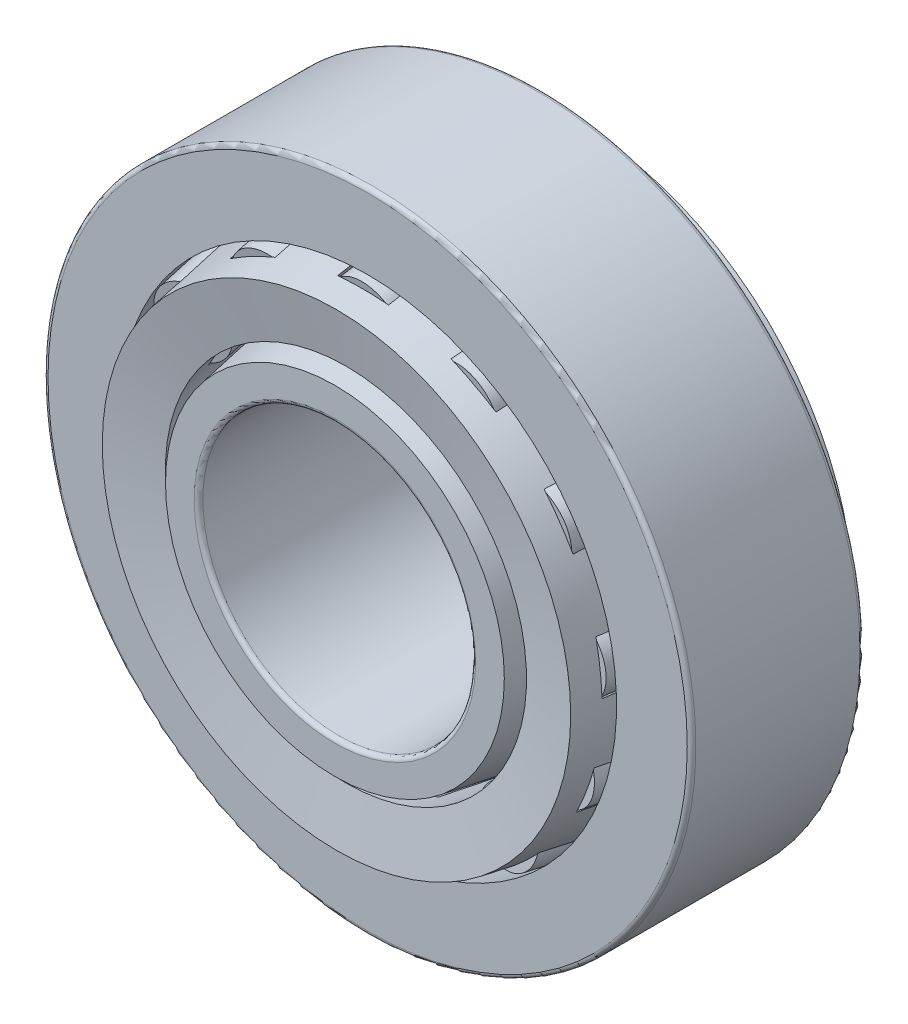
SolidWorks part; units mm, degrees
ref_plane "Front Plane" through (0, 0, 0) normal (0, 0, 1) x (1, 0, 0)
ref_plane "Top Plane" through (0, 0, 0) normal (0, 1, 0) x (1, 0, 0)
ref_plane "Right Plane" through (0, 0, 0) normal (1, 0, 0) x (0, 0, -1)
sketch "Sketch1" plane through (0, 0, 0) normal (1, 0, 0) x (0, 0, -1)
  line L0 (-8.3185, 0) -> (8.3185, 0) construction
  line L1 (0, 0) -> (0, 22.6219) construction
  line L2 (-8.3185, 9.525) -> (8.3185, 9.525) construction
  line L3 (8.3185, 9.525) -> (8.3185, 14.7638) construction
  line L4 (8.3185, 14.7638) -> (-8.3185, 11.8302) construction
  line L5 (-8.3185, 11.8302) -> (-8.3185, 9.525) construction
  line L7 (-6.0325, 22.6219) -> (6.0325, 22.6219)
  line L8 (6.0325, 22.6219) -> (6.0325, 19.5105)
  line L9 (6.0325, 19.5105) -> (-6.0325, 17.3831)
  line L10 (-6.0325, 17.3831) -> (-6.0325, 22.6219)
  line L12 (8.4538, 19.9375) -> (9.3345, 14.9429) construction
  line L13 (-7.4378, 11.9855) -> (-8.3185, 16.98) construction
  line L14 (-8.3185, 11.8302) -> (-7.4378, 11.9855) construction
  line L15 (-8.3185, 11.8302) -> (9.3345, 14.9429) construction
  line L20 (-8.3185, -11.8302) -> (9.3345, -14.9429) construction
  line L21 (-8.3185, -11.8302) -> (-7.4378, -11.9855) construction
  line L22 (-7.4378, -11.9855) -> (-8.3185, -16.98) construction
  line L23 (8.4538, -19.9375) -> (9.3345, -14.9429) construction
  line L24 (-8.3185, -11.8302) -> (-8.3185, -9.525) construction
  line L25 (8.3185, -14.7638) -> (-8.3185, -11.8302) construction
  line L26 (8.3185, -9.525) -> (8.3185, -14.7638) construction
  line L27 (-8.3185, -9.525) -> (8.3185, -9.525) construction
  line L28 (-6.0325, -17.3831) -> (-6.0325, -22.6219) construction
  line L29 (6.0325, -19.5105) -> (-6.0325, -17.3831) construction
  line L30 (6.0325, -22.6219) -> (6.0325, -19.5105) construction
  line L31 (-6.0325, -22.6219) -> (6.0325, -22.6219) construction
  point P5 (0, 9.525)
  point P37 (0, -9.525)
  dimension "OD" = 45.2437
  dimension "Shaft Dia" = 19.05
  dimension "D1" = 100
  dimension "D2" = 13.0969
  dimension "D3" = 5.2388
revolve "Revolve1" add sketch "Sketch1" angle 360 about L0
sketch "Sketch5" plane through (0, 0, 0) normal (1, 0, 0) x (0, 0, -1)
  line L0 (8.3185, 14.7638) -> (-8.3185, 11.8302) construction
  line L1 (8.3185, 14.7638) -> (-8.3185, 11.8302)
  line L2 (-8.3185, 11.8302) -> (-8.3185, 9.525)
  line L3 (-8.3185, 9.525) -> (8.3185, 9.525)
  line L4 (8.3185, 9.525) -> (8.3185, 14.7638)
revolve "Revolve4" add sketch "Sketch5" angle 360 about L0
sketch "Sketch2" plane through (0, 0, 0) normal (1, 0, 0) x (0, 0, -1)
  line L0 (-8.2084, 16.3557) -> (-7.5479, 12.6098)
  line L1 (6.0325, 18.8668) -> (8.5639, 19.3131)
  line L2 (-7.5479, 12.6098) -> (6.0325, 15.0044)
  line L3 (8.4538, 19.9375) -> (9.3345, 14.9429) construction
  line L4 (6.0325, 15.0044) -> (6.0325, 18.8668) construction
  line L5 (6.0325, 18.8668) -> (-8.2084, 16.3557)
  line L6 (6.0325, 19.5105) -> (-6.0325, 17.3831) construction
  line L7 (8.3185, 14.7638) -> (-8.3185, 11.8302) construction
  line L8 (-8.3185, 16.98) -> (6.0325, 19.5105) construction
  line L9 (-7.4378, 11.9855) -> (9.3345, 14.9429) construction
  line L10 (8.5639, 19.3131) -> (9.2244, 15.5672)
  line L11 (-8.3185, 16.98) -> (-8.2084, 16.3557) construction
  line L12 (6.0325, -22.6219) -> (6.0325, 22.6219) construction
  line L13 (6.0325, 22.6219) -> (6.0325, 19.5105) construction
  line L14 (9.2244, 15.5672) -> (6.0325, 15.0044)
  line L15 (-7.5479, 12.6098) -> (-7.4378, 11.9855) construction
  line L16 (0, 0) -> (-8.3185, 0) construction
  line L17 (-8.3185, 11.8302) -> (-8.3185, -11.8302) construction
  line L18 (-7.5479, -12.6098) -> (-7.4378, -11.9855) construction
  line L19 (-8.3185, -16.98) -> (-8.2084, -16.3557) construction
  line L20 (-7.4378, -11.9855) -> (9.3345, -14.9429) construction
  line L21 (-8.3185, -16.98) -> (6.0325, -19.5105) construction
  line L22 (6.0325, -15.0044) -> (6.0325, -18.8668) construction
  line L23 (9.2244, -15.5672) -> (6.0325, -15.0044) construction
  line L24 (8.5639, -19.3131) -> (9.2244, -15.5672) construction
  line L25 (6.0325, -18.8668) -> (-8.2084, -16.3557) construction
  line L26 (-7.5479, -12.6098) -> (6.0325, -15.0044) construction
  line L27 (6.0325, -18.8668) -> (8.5639, -19.3131) construction
  line L28 (-8.2084, -16.3557) -> (-7.5479, -12.6098) construction
  dimension "D2" = 3.8037
  dimension "D1" = 5.0716
revolve "Revolve2" add sketch "Sketch2" angle 360 about L0
sketch "Sketch3" plane through (0, 0, 0) normal (1, 0, 0) x (0, 0, -1)
  line L0 (-7.8782, 14.4828) -> (6.0325, 16.9356) construction
  line L1 (-8.2084, 16.3557) -> (-7.5479, 12.6098) construction
  line L2 (6.0325, 15.0044) -> (6.0325, 18.8668) construction
  line L3 (-6.0325, 14.8082) -> (-6.4728, 17.3055)
  line L5 (-6.4728, 17.3055) -> (5.5922, 19.4329)
  line L6 (5.5922, 19.4329) -> (6.0325, 16.9356)
  line L7 (6.0325, 16.9356) -> (-6.0325, 14.8082)
  line L11 (-7.8782, 14.4828) -> (-6.0325, 14.8082) construction
  line L12 (-6.0325, 22.6219) -> (-6.0325, -22.6219) construction
  line L13 (-7.8782, 14.4828) -> (-6.0325, 14.8082) construction
revolve "Cut-Revolve1" cut sketch "Sketch3" angle 360 about L0
sketch "Sketch4" plane through (0, 0, 0) normal (1, 0, 0) x (0, 0, -1)
  line L0 (-6.4508, 17.1804) -> (5.6142, 19.3078)
  line L1 (5.6142, 19.3078) -> (6.0325, 16.9356)
  line L2 (6.0325, 16.9356) -> (-6.0325, 14.8082)
  line L3 (-6.0325, 14.8082) -> (-7.8782, 14.4828) construction
  line L4 (-6.0325, 14.8082) -> (-6.4508, 17.1804)
  line L5 (-7.8782, 14.4828) -> (-6.0325, 14.8082) construction
  line L6 (6.0325, 16.9356) -> (-6.0325, 14.8082) construction
  line L7 (6.0325, 19.5105) -> (-6.0325, 17.3831) construction
  line L8 (0, 0) -> (-8.3185, 0) construction
  line L9 (-8.3185, 0) -> (8.3185, 0) construction
  line L10 (-7.8782, -14.4828) -> (-6.0325, -14.8082) construction
  line L11 (-6.0325, -14.8082) -> (-7.8782, -14.4828) construction
  line L12 (-6.0325, -14.8082) -> (-6.4508, -17.1804) construction
  line L13 (6.0325, -16.9356) -> (-6.0325, -14.8082) construction
  line L14 (5.6142, -19.3078) -> (6.0325, -16.9356) construction
  line L15 (-6.4508, -17.1804) -> (5.6142, -19.3078) construction
  dimension "D1" = 0.127
revolve "Revolve3" add sketch "Sketch4" angle 360 about L0
sketch "Sketch7" plane through (0, 0, 0) normal (0, 0, 1) x (1, 0, 0)
  line L0 (0, 0) -> (-1.9265, 11.6906) construction
  line L1 (0, 0) -> (1.9265, 11.6906) construction
  ellipse E0 centre (0, 14.8082) end of major axis (-2.4088, 14.8082) minor radius 2.3722 construction
  dimension "D1" = 18.716
ref_axis "Axis1" through (0, 0, -8.3185) along (0, 0, 1)
pattern_circular "CirPattern2" count 13 over 360 about axis through (0, 0, -8.3185) along (0, 0, 1) of bodies 403
pattern_circular "CirPattern1" count 13 over 360 about axis through (0, 0, -8.3185) along (0, 0, 1) of "Cut-Revolve1"
fillet "Fillet1" radius 0.3016 2 edges at (0, -22.6219, -6.0325) (0, -22.6219, 6.0325)
fillet "Fillet2" radius 0.3016 2 edges at (0, -9.525, -8.3185) (0, -9.525, 8.3185)
sketch "Sketch6" plane through (0, 0, 0) normal (1, 0, 0) x (0, 0, -1)
  line L0 (-45.2734, 22.6219) -> (-45.2734, 17.3831)
  line L1 (-45.2734, 17.3831) -> (-33.2084, 19.5105)
  line L2 (-33.2084, 19.5105) -> (-33.2084, 22.6219)
  line L3 (-33.2084, 22.6219) -> (-45.2734, 22.6219)
  line L4 (-6.0325, 22.6219) -> (6.0325, 22.6219) construction
  line L5 (6.0325, 22.6219) -> (6.0325, 19.5105) construction
  line L6 (6.0325, 19.5105) -> (-6.0325, 17.3831) construction
  line L7 (-8.2084, -16.3557) -> (-8.2084, 16.3557) construction
  dimension "D1" = 25
revolve "Revolve5" [suppressed] add sketch "Sketch6" angle 360 about L0
fillet "Fillet3" [suppressed] radius 0.3016
delete or keep bodies "Body-Delete1" [suppressed] type delete bodies bodies 399
equation "\"D3@Sketch1\" = \"D2@Sketch1\"/2.5"
equation "\"D2@Sketch2\" = \"D1@Sketch2\"*.75"
equation "\"D1@Fillet1\"= \"Width@Sketch1\" * .025"
equation "\"D1@Fillet2\" = \"D1@Fillet1\""
equation "\"D1@Fillet3\" = \"D1@Fillet1\""
equation "\"Rollers@CirPattern2\"=(360/\"D1@Sketch7\")/1.50"
equation "\"D1@CirPattern1\"=\"Rollers@CirPattern2\""
